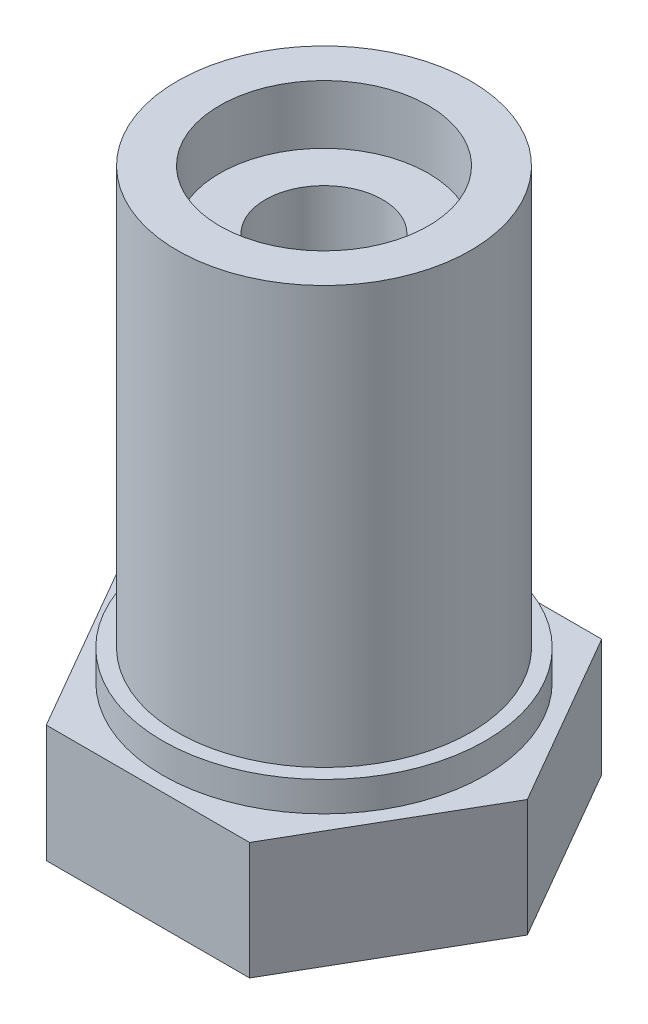
SolidWorks part; units mm, degrees
ref_plane "Front Plane" through (0, 0, 0) normal (0, 0, 1) x (1, 0, 0)
ref_plane "Top Plane" through (0, 0, 0) normal (0, 1, 0) x (1, 0, 0)
ref_plane "Right Plane" through (0, 0, 0) normal (1, 0, 0) x (0, 0, -1)
sketch "Sketch1" plane through (0, 0, 0) normal (0, 1, 0) x (1, 0, 0)
  line L1 (3.4641, 6) -> (-3.4641, 6)
  line L2 (-3.4641, 6) -> (-6.9282, 0)
  line L3 (-6.9282, 0) -> (-3.4641, -6)
  line L4 (-3.4641, -6) -> (3.4641, -6)
  line L5 (3.4641, -6) -> (6.9282, 0)
  line L6 (6.9282, 0) -> (3.4641, 6)
  circle A0 centre (0, 0) radius 6 construction
  dimension "D1" = 12
extrude "Boss-Extrude1" add sketch "Sketch1" along normal blind 4
sketch "Sketch2" plane through (0, 4, 0) normal (0, 1, 0) x (1, 0, 0)
  circle A0 centre (0, 0) radius 5
  circle A1 centre (0, 0) radius 5.5
  dimension "D1" = 11
  dimension "D2" = 10
extrude "Boss-Extrude2" add sketch "Sketch2" along normal blind 1.016
extrude "Boss-Extrude3" add sketch "Sketch2<2>" along normal blind 15.24 contours A0 region at (0, 4, 0)
sketch "Sketch2<2>" plane through (0, 4, 0) normal (0, 1, 0) x (1, 0, 0) same geometry as "Sketch2"
sketch "Sketch4" plane through (0, 19.24, 0) normal (0, 1, 0) x (1, 0, 0)
  circle A0 centre (0, 0) radius 3.556
  circle A1 centre (0, 0) radius 2
  dimension "D1" = 7.112
  dimension "D2" = 4
extrude "Cut-Extrude2" cut sketch "Sketch4" against normal through all contours A1 region at (0, 19.24, 0)
extrude "Cut-Extrude3" cut sketch "Sketch4<3>" against normal blind 2
sketch "Sketch4<3>" plane through (0, 19.24, 0) normal (0, 1, 0) x (1, 0, 0) same geometry as "Sketch4"
